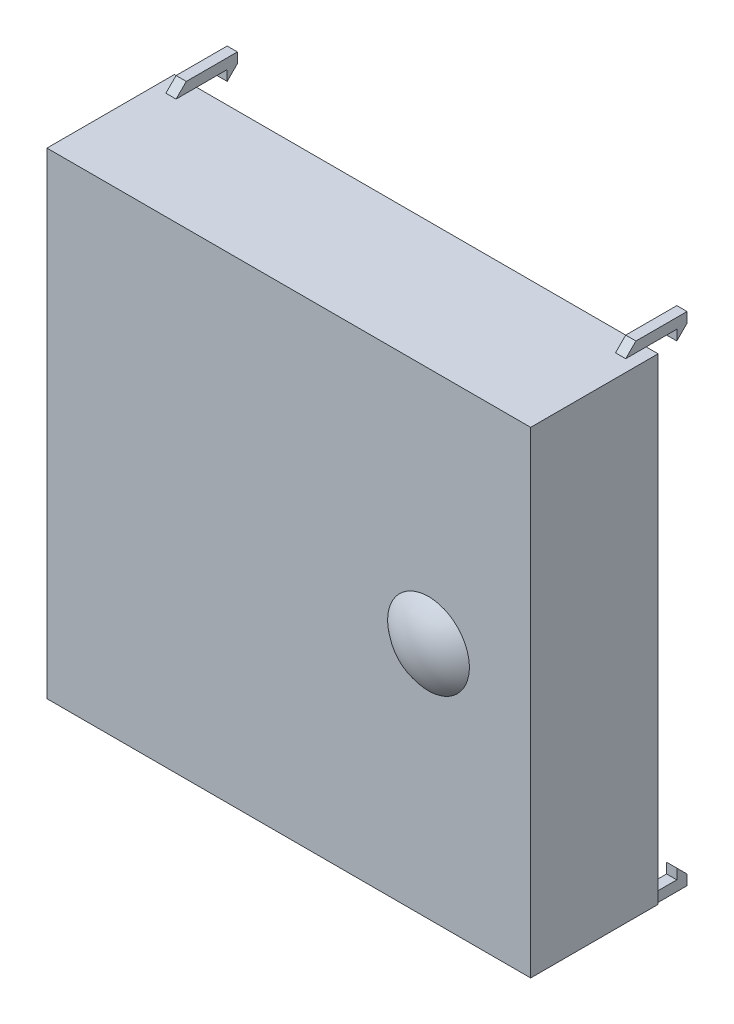
SolidWorks part; units mm, degrees
ref_plane "Front Plane" through (0, 0, 0) normal (0, 0, 1) x (1, 0, 0)
ref_plane "Top Plane" through (0, 0, 0) normal (0, 1, 0) x (1, 0, 0)
ref_plane "Right Plane" through (0, 0, 0) normal (1, 0, 0) x (0, 0, -1)
sketch "Sketch1" plane through (0, 0, 0) normal (0, 0, 1) x (1, 0, 0)
  line L0 (10.75, -9.75) -> (-121.1, -9.75) construction
  line L1 (10.75, 60.25) -> (-60.25, 60.25)
  line L2 (10.75, 60.25) -> (10.75, -9.75)
  line L3 (10.75, -9.75) -> (-60.25, -9.75)
  line L4 (-60.25, 60.25) -> (-60.25, -9.75)
  line L5 (9.25, 58.75) -> (-58.75, 58.75)
  line L6 (-58.75, 58.75) -> (-58.75, -8.25)
  line L7 (9.25, -8.25) -> (-58.75, -8.25)
  line L8 (9.25, 58.75) -> (9.25, -8.25)
  dimension "D1" = 71
  dimension "D2" = 1.5
extrude "Boss-Extrude1" add sketch "Sketch1" along normal blind 17.2
extrude "Boss-Extrude2" add sketch "Sketch1<2>" along normal blind 1.5 from surface contours L4 L3 L2 L1 starting at face at (-24.75, 25.25, 17.2)
sketch "Sketch1<2>" plane through (0, 0, 0) normal (0, 0, 1) x (1, 0, 0) same geometry as "Sketch1"
sketch "Sketch3" plane through (0, 60.25, 0) normal (0, 1, 0) x (1, 0, 0)
  line L0 (-58.75, -3) -> (-60.25, -3) construction
  line L1 (-58.75, -3) -> (-57.25, -3)
  line L2 (-58.75, -3) -> (-58.75, 0)
  line L3 (-58.75, 0) -> (-57.25, 0)
  line L4 (-57.25, -3) -> (-57.25, 0)
  line L5 (-60.25, -18.7) -> (-60.25, 0) construction
  line L6 (10.75, 0) -> (-121.1, 0) construction
  dimension "D1" = 1.5
  dimension "D2" = 3
sketch "Sketch4" plane through (-60.25, 0, 0) normal (-1, 0, 0) x (0, 0, 1)
  line L0 (3, 60.25) -> (0, 60.25) construction
  line L1 (3, 60.25) -> (-4.5, 60.25)
  line L2 (0, -9.75) -> (0, 60.25) construction
  line L3 (1.5, 61.75) -> (-4.5, 61.75)
  line L4 (0, 60.25) -> (-36.6375, 60.25) construction
  line L5 (3, 60.25) -> (0, 60.25) construction
  line L6 (3, 60.25) -> (1.5, 61.75)
  line L7 (1.5, 61.75) -> (1.5, 60.25) construction
  line L8 (-36.6375, 58.75) -> (-32.3875, 58.75) construction
  line L9 (-4.5, 61.75) -> (-6, 61.75)
  line L10 (-4.5, 61.75) -> (-4.5, 58.75)
  line L12 (-6, 61.75) -> (-6, 60.25)
  line L13 (-4.5, 58.75) -> (-6, 60.25)
  line M12 (18.7, 60.25) -> (0, 60.25)
  dimension "D1" = 1.5
  dimension "D2" = 3
  dimension "D3" = 45
  dimension "D4" = 6
extrude "Boss-Extrude4" add sketch "Sketch4" against normal blind 1.5 from offset 1.75 contours L6 L7 M12 | L7 L3 L10 L1 | L13 L10 L9 L12 region at (-60.25, 60.75, 2) region at (-60.25, 61, -1.5) region at (-60.25, 60.5833, -5.1667) offset against normal yes
ref_plane "Plane1" through (0, 25.25, 0) normal (0, 1, 0) x (1, 0, 0)
ref_plane "Plane2" through (-24.75, 0, 0) normal (1, 0, 0) x (0, 0, -1)
mirror "Mirror1" about plane through (0, 25.25, 0) normal (0, 1, 0) of "Boss-Extrude4"
mirror "Mirror2" about plane through (-24.75, 0, 0) normal (1, 0, 0) of "Mirror1", "Boss-Extrude4"
ref_plane "Plane3" through (0, 0, 20.975) normal (0, 0, 1) x (1, 0, 0)
sketch "Sketch5" plane through (0, 0, 18.7) normal (0, 0, 1) x (1, 0, 0)
  line L0 (10.75, 60.25) -> (10.75, -9.75) construction
  line L1 (1.75, 25.25) -> (10.75, 25.25) construction
  circle A0 centre (-4.25, 25.25) radius 6
  point P4 (10.75, 25.25)
  dimension "D1" = 12
  dimension "D2" = 9
extrude "Boss-Extrude5" add sketch "Sketch5" along normal up to surface (2.275 mm away) up to plane "Plane3"
fillet "Fillet1" radius 9 1 edges at (1.75, 25.25, 20.975)
equation "\"D1@Boss-Extrude1\"=14.2+3"
equation "\"D19@Boss-Extrude4\"=1.50mm+.25"
